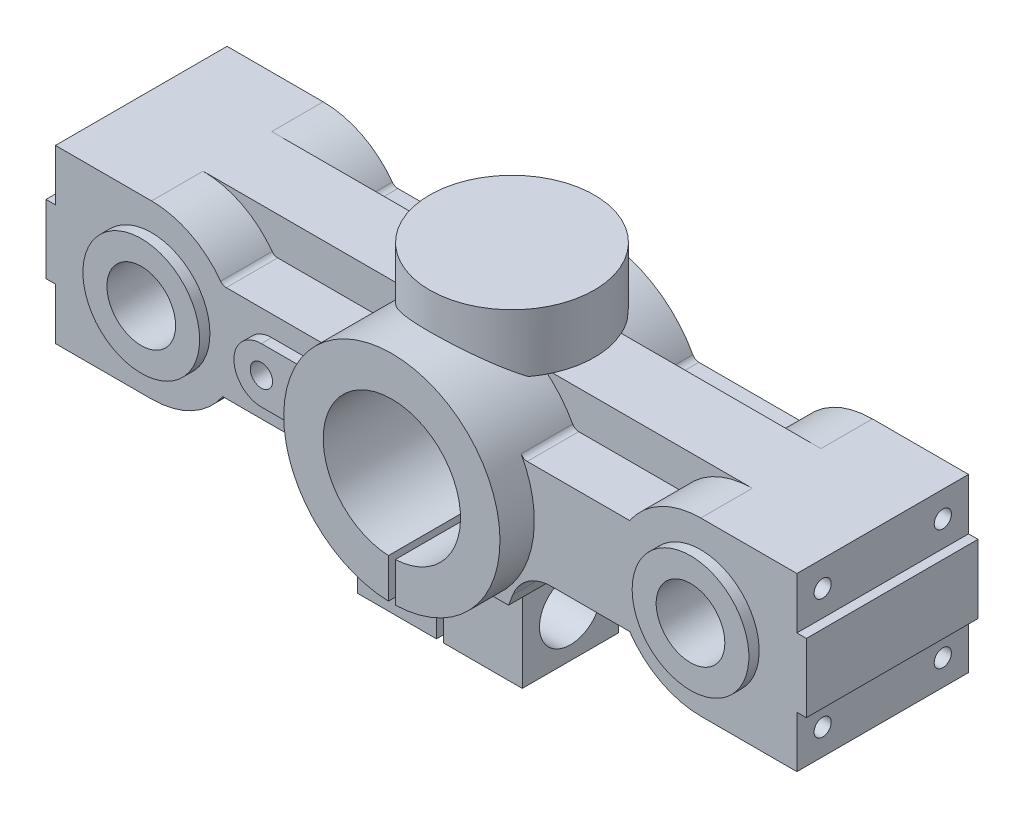
SolidWorks part; units mm, degrees
ref_plane "前视基准面" through (0, 0, 0) normal (0, 0, 1) x (1, 0, 0)
ref_plane "上视基准面" through (0, 0, 0) normal (0, 1, 0) x (1, 0, 0)
ref_plane "右视基准面" through (0, 0, 0) normal (1, 0, 0) x (0, 0, -1)
sketch "草图1" plane through (0, 0, 0) normal (0, 0, 1) x (1, 0, 0)
  circle A0 centre (0, 0) radius 31.5
  dimension "D1" = 63
extrude "凸台-拉伸1" add sketch "草图1" along normal blind 60
sketch "草图4" plane through (0, 0, 0) normal (0, 0, 1) x (1, 0, 0)
  line L0 (0, 0) -> (0, 42.2899) construction
  line L1 (-110.75, 25) -> (110.75, 25)
  line L2 (-110.75, 25) -> (-110.75, -25)
  line L3 (-110.75, -25) -> (110.75, -25)
  line L4 (110.75, 25) -> (110.75, -25)
  line L5 (0, 0) -> (41.5096, 0) construction
  dimension "D1" = 221.5
  dimension "D2" = 50
extrude "凸台-拉伸2" add sketch "草图4" along normal blind 50
sketch "草图5" plane through (0, 0, 50) normal (0, 0, 1) x (1, 0, 0)
  line L0 (0, 0) -> (0, 50.6309) construction
  line L1 (-110.75, 25) -> (-108, 25)
  line L2 (-110.75, 25) -> (-110.75, 10)
  line L3 (-110.75, 10) -> (-108, 10)
  line L4 (-108, 25) -> (-108, 10)
  line L5 (0, 0) -> (-122.6141, 0) construction
  line L6 (-108, -25) -> (-108, -10)
  line L7 (-110.75, -10) -> (-108, -10)
  line L8 (-110.75, -25) -> (-110.75, -10)
  line L9 (-110.75, -25) -> (-108, -25)
  line L10 (110.75, -25) -> (108, -25)
  line L11 (110.75, -25) -> (110.75, -10)
  line L12 (110.75, -10) -> (108, -10)
  line L13 (108, -25) -> (108, -10)
  line L14 (108, 25) -> (108, 10)
  line L15 (110.75, 10) -> (108, 10)
  line L16 (110.75, 25) -> (110.75, 10)
  line L17 (110.75, 25) -> (108, 25)
  dimension "D1" = 216
  dimension "D2" = 20
extrude "切除-拉伸1" cut sketch "草图5" against normal through all
sketch "草图6" plane through (0, 0, 50) normal (0, 0, 1) x (1, 0, 0)
  line L0 (0, 0) -> (0, 52.2485) construction
  circle A0 centre (-80, 0) radius 17
  circle A1 centre (80, 0) radius 17
  dimension "D2" = 34
  dimension "D1" = 160
extrude "凸台-拉伸3" add sketch "草图6" along normal blind 3
sketch "草图7" plane through (0, 0, 53) normal (0, 0, 1) x (1, 0, 0)
  circle A0 centre (-80, 0) radius 10
  circle A1 centre (80, 0) radius 10
  dimension "D1" = 20
extrude "切除-拉伸2" cut sketch "草图7" against normal blind 45
sketch "草图8" plane through (0, 0, 8) normal (0, 0, 1) x (1, 0, 0)
  circle A0 centre (-80, 0) radius 1.5
  circle A1 centre (80, 0) radius 1.5
  dimension "D1" = 3
extrude "切除-拉伸3" cut sketch "草图8" against normal through all
sketch "草图9" plane through (0, 0, 50) normal (0, 0, 1) x (1, 0, 0)
  line L0 (-30.4672, 8) -> (-45, 8)
  line L1 (-45, -8) -> (-30.4672, -8)
  line L2 (0, 0) -> (-45, 0) construction
  circle A0 centre (0, 0) radius 31.5 construction
  arc A1 (-45, 8) -> (-45, -8) centre (-45, 0) ccw
  arc A2 (-19.1638, 25) -> (-19.1638, -25) centre (0, 0) ccw construction
  arc A3 (-30.4672, 8) -> (-30.4672, -8) centre (0, 0) ccw
  dimension "D2" = 8
  dimension "D1" = 45
extrude "凸台-拉伸4" add sketch "草图9" along normal up to surface (3 mm away) up to face at (-70, 0, 53)
sketch "草图10" plane through (0, 0, 53) normal (0, 0, 1) x (1, 0, 0)
  circle A0 centre (-45, 0) radius 3.25
  dimension "D1" = 6.5
extrude "切除-拉伸4" cut sketch "草图10" against normal through all
ref_plane "基准面1" through (0, 0, 35) normal (0, 0, -1) x (-1, 0, 0)
sketch "草图11" plane through (0, 0, 35) normal (0, 0, 1) x (1, 0, 0)
  line L0 (-59.2877, 14) -> (-28.2179, 14)
  line L1 (0, 0) -> (-80, 0) construction
  line L2 (0, 0) -> (0, 47.0472) construction
  line L3 (-80, 25) -> (-19.1638, 25)
  line L4 (80, 25) -> (19.1638, 25)
  line L5 (59.2877, 14) -> (28.2179, 14)
  arc A0 (-59.2877, 14) -> (-80, 25) centre (-80, 0) ccw
  circle A1 centre (0, 0) radius 31.5 construction
  arc A2 (19.1638, 25) -> (28.2179, 14) centre (0, 0) cw
  arc A3 (-19.1638, 25) -> (-28.2179, 14) centre (0, 0) ccw
  arc A4 (59.2877, 14) -> (80, 25) centre (80, 0) cw
  dimension "D1" = 50
  dimension "D2" = 14
extrude "切除-拉伸5" cut sketch "草图11" along normal through all
ref_plane "基准面2" through (0, 0, 25) normal (0, 0, -1) x (-1, 0, 0)
mirror "镜向1" about plane through (0, 0, 25) normal (0, 0, -1) of "切除-拉伸5"
sketch "草图12" plane through (0, 25, 0) normal (0, 1, 0) x (1, 0, 0)
  line L0 (-19.1638, -15) -> (19.1638, -35) construction
  circle A0 centre (0, -25) radius 24
  dimension "D1" = 48
extrude "凸台-拉伸5" add sketch "草图12" along normal blind 17
ref_plane "基准面3" through (0, 0, 18) normal (0, 0, -1) x (-1, 0, 0)
sketch "草图13" plane through (0, 0, 18) normal (0, 0, -1) x (-1, 0, 0)
  line L0 (108, -25) -> (19.1638, -25) construction
  line L1 (24, -25) -> (-24, -25)
  line L2 (24, -25) -> (24, -48)
  line L3 (24, -48) -> (-24, -48)
  line L4 (-24, -25) -> (-24, -48)
  line L5 (0, 0) -> (0, -71.8357) construction
  dimension "D1" = 48
  dimension "D2" = 48
extrude "凸台-拉伸6" add sketch "草图13" against normal blind 28
sketch "草图14" plane through (0, 0, 50) normal (0, 0, 1) x (1, 0, 0)
  line L0 (-80, -25) -> (-24, -25)
  line L1 (-59.2877, -14) -> (-28.2179, -14)
  line L2 (-28.2179, -14) -> (-24, -25)
  line L3 (0, 0) -> (0, 60.5232) construction
  line L4 (28.2179, -14) -> (24, -25)
  line L5 (59.2877, -14) -> (28.2179, -14)
  line L6 (80, -25) -> (24, -25)
  arc A0 (-80, -25) -> (-59.2877, -14) centre (-80, 0) ccw
  arc A1 (-59.2877, 14) -> (-80, 25) centre (-80, 0) ccw construction
  circle A2 centre (0, 0) radius 31.5 construction
  arc A4 (80, -25) -> (59.2877, -14) centre (80, 0) cw
  dimension "D1" = 14
extrude "切除-拉伸6" cut sketch "草图14" against normal through all
fillet "圆角1" radius 12 2 edges at (-28.2179, -14, 25) (28.2179, -14, 25)
sketch "草图15" plane through (-24, 0, 0) normal (-1, 0, 0) x (0, 0, 1)
  line L0 (0, -25) -> (0, -10) construction
  line L1 (32, -24.6077) -> (23, -29.8038)
  line L2 (23, -29.8038) -> (23, -40.1962)
  line L3 (23, -40.1962) -> (32, -45.3923)
  line L4 (32, -45.3923) -> (41, -40.1962)
  line L5 (41, -40.1962) -> (41, -29.8038)
  line L6 (41, -29.8038) -> (32, -24.6077)
  line L7 (46, -48) -> (18, -48) construction
  circle A0 centre (32, -35) radius 9 construction
  dimension "D1" = 32
  dimension "D2" = 18
  dimension "D3" = 13
extrude "切除-拉伸7" cut sketch "草图15" against normal blind 8
sketch "草图17" plane through (24, 0, 0) normal (1, 0, 0) x (0, 0, -1)
  line L0 (-32, -24.6077) -> (-32, -45.3923) construction
  circle A0 centre (-32, -35) radius 9
  dimension "D1" = 18
extrude "切除-拉伸8" cut sketch "草图17" against normal blind 13
sketch "草图18" plane through (11, 0, 0) normal (1, 0, 0) x (0, 0, -1)
  circle A0 centre (-32, -35) radius 5.5
  dimension "D1" = 11
extrude "切除-拉伸9" cut sketch "草图18" against normal through all
sketch "草图19" plane through (0, 0, 60) normal (0, 0, 1) x (1, 0, 0)
  circle A0 centre (0, 0) radius 20
  dimension "D1" = 40
extrude "切除-拉伸10" cut sketch "草图19" against normal through all
sketch "草图20" plane through (0, 0, 60) normal (0, 0, 1) x (1, 0, 0)
  line L0 (0, 0) -> (0, -73.0421) construction
  line L1 (-1, -6.397) -> (1, -6.397)
  line L2 (-1, -6.397) -> (-1, -58.4837)
  line L3 (-1, -58.4837) -> (1, -58.4837)
  line L4 (1, -6.397) -> (1, -58.4837)
  dimension "D1" = 2
extrude "切除-拉伸11" cut sketch "草图20" against normal through all
hole_wizard "M6x1.0 螺纹孔1" positions "草图22" profile "草图21" tap size "M6x1.0" standard "JIS"
sketch "草图22" plane through (-108, 0, 0) normal (-1, 0, 0) x (0, 0, 1)
  line L0 (25, 25) -> (25, -25) construction
  line L1 (35, 25) -> (15, 25) construction
  line L2 (0, -25) -> (50, -25) construction
  line L4 (0, 0) -> (60, 0.0079) construction
  line L5 (60, -31.4841) -> (60, 31.5) construction
  point P0 (42.5, 17.5056)
  point P1 (7.5, 17.5056)
  point P18 (7.5046, -17.5036)
  point P19 (42.5046, -17.4944)
  dimension "D1" = 35
  dimension "D2" = 35
sketch "草图21" plane through (-108, 17.5056, 42.5) normal (0, 1, 0) x (0, 0, 1)
  line L0 (0, 0) -> (0, 16.5022)
  line L1 (0, 16.5022) -> (2.5, 15)
  line L2 (2.5, 15) -> (2.5, 0)
  line L5 (2.5, 0) -> (0, 0)
  line L10 (0, 16.5022) -> (-2.5, 15) construction
  line L11 (0, -6.35) -> (0, 107.95) construction
  dimension "螺纹孔钻头直径" = 5
  dimension "螺纹孔钻头深度" = 15
  dimension "导头角度" = 118
cosmetic thread "孔螺蚊线1" parameters "D1"=12, "D2"=6
cosmetic thread "孔螺蚊线2" parameters "D1"=12, "D2"=6
cosmetic thread "孔螺蚊线3" parameters "D1"=12, "D2"=6
cosmetic thread "孔螺蚊线4" parameters "D1"=12, "D2"=6
mirror "镜向2" about plane through (0, 0, 0) normal (1, 0, 0) of "M6x1.0 螺纹孔1"
fillet "圆角2" radius 2 4 edges at (28.2179, 14, 42.5) (28.2179, 14, 7.5) (-59.2877, 14, 7.5) (-59.2877, 14, 42.5)
